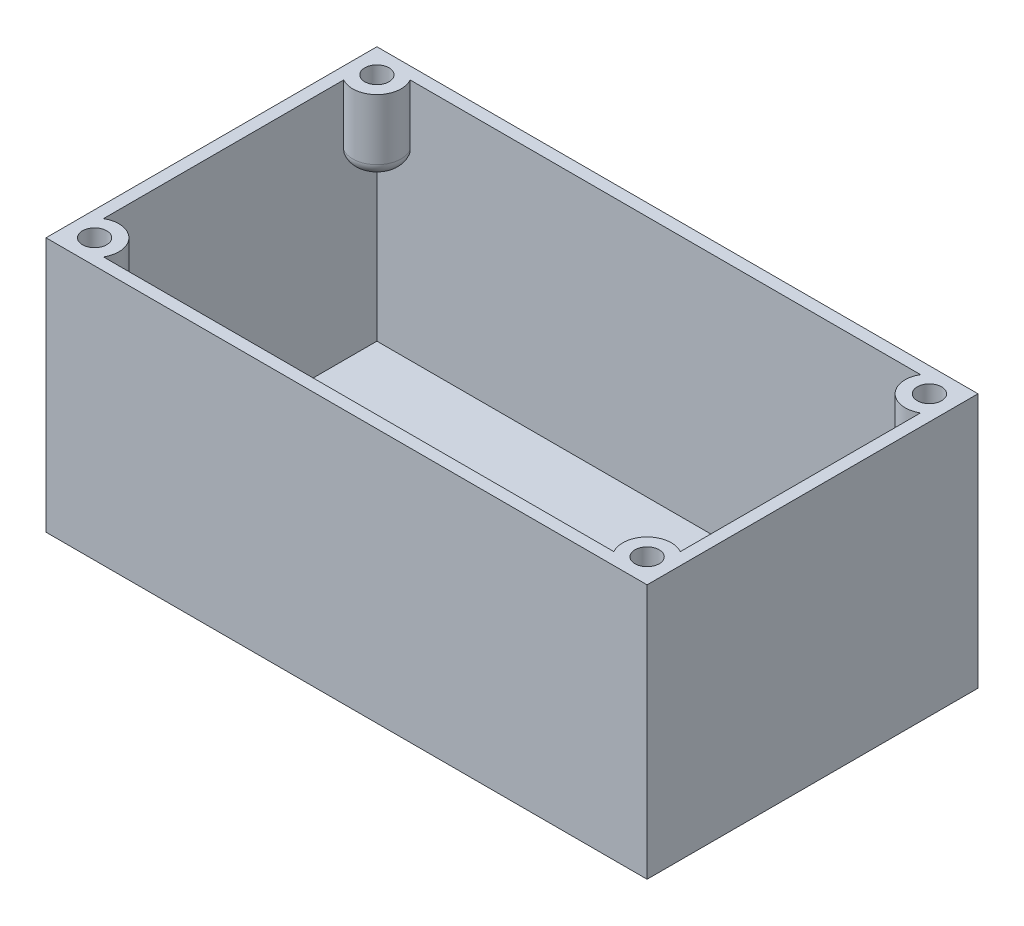
SolidWorks part; units mm, degrees
note: The reader was unsure of these and kept them because the rebuilt part matched: shared geometry of "Sketch4<2>", "Sketch7<4>".
ref_plane "Front Plane" through (0, 0, 0) normal (0, 0, 1) x (1, 0, 0)
ref_plane "Top Plane" through (0, 0, 0) normal (0, 1, 0) x (1, 0, 0)
ref_plane "Right Plane" through (0, 0, 0) normal (1, 0, 0) x (0, 0, -1)
sketch "Sketch1" plane through (0, 0, 0) normal (0, 1, 0) x (1, 0, 0)
  line L1 (-49.5, 27.25) -> (49.5, 27.25)
  line L2 (-49.5, 27.25) -> (-49.5, -27.25)
  line L3 (-49.5, -27.25) -> (49.5, -27.25)
  line L4 (49.5, 27.25) -> (49.5, -27.25)
  point P4 (0, 27.25)
  point P6 (-49.5, 0)
  dimension "D1" = 99
  dimension "D2" = 54.5
extrude "Boss-Extrude1" add sketch "Sketch1" along normal blind 2
sketch "Sketch2" plane through (0, 2, 0) normal (0, 1, 0) x (1, 0, 0)
  line L1 (-49.5, 27.25) -> (49.5, 27.25)
  line L2 (-49.5, 27.25) -> (-49.5, -27.25)
  line L3 (-49.5, -27.25) -> (49.5, -27.25)
  line L4 (49.5, 27.25) -> (49.5, -27.25)
  line L5 (-47.5, 25.25) -> (47.5, 25.25)
  line L6 (-47.5, 25.25) -> (-47.5, -25.25)
  line L7 (-47.5, -25.25) -> (47.5, -25.25)
  line L8 (47.5, 25.25) -> (47.5, -25.25)
  point P10 (0, 25.25)
  point P11 (0, 27.25)
  point P12 (-47.5, 0)
  point P13 (-49.5, 0)
  dimension "D1" = 2
  dimension "D2" = 2
extrude "Boss-Extrude2" add sketch "Sketch2" along normal blind 40
sketch "Sketch4" plane through (0, 2, 0) normal (0, 1, 0) x (1, 0, 0)
  line L0 (-47.5, -25.25) -> (47.5, -25.25) construction
  line L1 (-47.5, 25.25) -> (-47.5, -25.25) construction
  line L2 (-41.5, -10.75) -> (-41.5, -19.25) construction
  circle A0 centre (-41.5, -19.25) radius 2
  circle A1 centre (-41.5, -10.75) radius 2
  circle A2 centre (-41.5, -19.25) radius 3.5
  circle A3 centre (-41.5, -10.75) radius 3.5
  dimension "D1" = 4
  dimension "D3" = 4
  dimension "D4" = 7
  dimension "D5" = 7
  dimension "D2" = 8.5
  dimension "D6" = 6
  dimension "D7" = 6
extrude "Boss-Extrude3" add sketch "Sketch4" along normal blind 8
extrude "Cut-Extrude1" cut sketch "Sketch4<2>" against normal up to surface (2 mm away) contours A1 | A0 up to face at (0, 0, 0)
sketch "Sketch4<2>" plane through (0, 2, 0) normal (0, 1, 0) x (1, 0, 0) same geometry as "Sketch4"
sketch "Sketch6" plane through (-47.5, 0, 0) normal (1, 0, 0) x (0, 0, -1)
  line L0 (-25.25, 42) -> (-25.25, 2) construction
  line L1 (-10.85, 14.7) -> (-19.15, 14.7)
  line L2 (-10.85, 14.7) -> (-10.85, 11.6)
  line L3 (-10.85, 11.6) -> (-19.15, 11.6)
  line L4 (-19.15, 14.7) -> (-19.15, 11.6)
  line L6 (-7.25, 10) -> (-14.25, 10) construction
  point P4 (-15, 14.7)
  dimension "D1" = 10.25
  dimension "D2" = 8.3
  dimension "D3" = 3.1
  dimension "D4" = 1.6
extrude "Cut-Extrude2" cut sketch "Sketch6" against normal up to surface (2 mm away) up to face at (-49.5, 21, 0)
sketch "Sketch7" plane through (0, 42, 0) normal (0, 1, 0) x (1, 0, 0)
  line L0 (0, 27.25) -> (0, -27.25) construction
  line L1 (49.5, 27.25) -> (-49.5, 27.25) construction
  line L2 (-49.5, -27.25) -> (49.5, -27.25) construction
  line L3 (-49.5, 0) -> (49.5, 0) construction
  line L4 (-49.5, 27.25) -> (-49.5, -27.25) construction
  line L5 (49.5, -27.25) -> (49.5, 27.25) construction
  line L8 (47.5, 25.25) -> (-47.5, 25.25) construction
  line L9 (-47.5, 25.25) -> (-47.5, -25.25) construction
  line L10 (-47.5, 19.7859) -> (-47.5, 25.25)
  line L11 (-47.5, 25.25) -> (-42.0359, 25.25)
  line L12 (47.5, 19.7859) -> (47.5, 25.25)
  line L13 (47.5, 25.25) -> (42.0359, 25.25)
  line L14 (47.5, -25.25) -> (42.0359, -25.25)
  line L15 (47.5, -19.7859) -> (47.5, -25.25)
  line L16 (-47.5, -19.7859) -> (-47.5, -25.25)
  line L17 (-47.5, -25.25) -> (-42.0359, -25.25)
  circle A0 centre (-45.5, 23.25) radius 2
  arc A1 (-42.0359, 25.25) -> (-47.5, 19.7859) centre (-45.5, 23.25) cw
  arc A2 (42.0359, 25.25) -> (47.5, 19.7859) centre (45.5, 23.25) ccw
  circle A3 centre (45.5, 23.25) radius 2
  arc A4 (42.0359, -25.25) -> (47.5, -19.7859) centre (45.5, -23.25) cw
  circle A5 centre (-45.5, -23.25) radius 2
  arc A6 (-42.0359, -25.25) -> (-47.5, -19.7859) centre (-45.5, -23.25) ccw
  circle A7 centre (45.5, -23.25) radius 2
  line M15 (47.5, -25.25) -> (-47.5, -25.25)
  line M16 (-47.5, -25.25) -> (-47.5, 25.25)
  line M17 (-47.5, 25.25) -> (47.5, 25.25)
  line M18 (47.5, 25.25) -> (47.5, -25.25)
  dimension "D3" = 4
  dimension "D4" = 4
  dimension "D1" = 4
  dimension "D2" = 4
extrude "Boss-Extrude4" add sketch "Sketch7" against normal blind 12 contours A1 L11 A0 M16 | A6 L16 A5 M15 | A7 A4 L14 M18 | L12 A3 A2 M17 | L10 A0 M17 | L15 A7 M15 | A3 L13 M18 | A0 L10 M17 | L17 A5 M16 | A7 L15 M15 | L13 A3 M18 | A5
extrude "Cut-Extrude3" cut sketch "Sketch7<4>" against normal blind 10 contours A0 | A5 | A7 | A3
sketch "Sketch7<4>" plane through (0, 42, 0) normal (0, 1, 0) x (1, 0, 0) same geometry as "Sketch7"
fillet "Fillet1" radius 2 4 edges at (42.6716, 30, 20.4216) (-42.6716, 30, 20.4216) (42.6716, 30, -20.4216) (-42.6716, 30, -20.4216)
